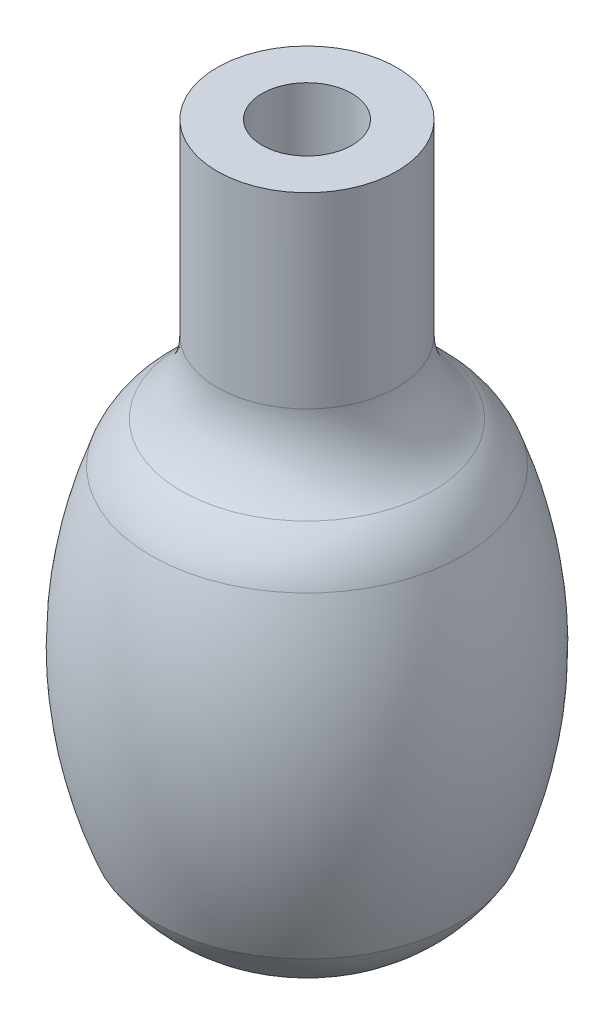
SolidWorks part; units mm, degrees
ref_plane "Front Plane" through (0, 0, 0) normal (0, 0, 1) x (1, 0, 0)
ref_plane "Top Plane" through (0, 0, 0) normal (0, 1, 0) x (1, 0, 0)
ref_plane "Right Plane" through (0, 0, 0) normal (1, 0, 0) x (0, 0, -1)
sketch "Sketch1" plane through (0, 0, 0) normal (1, 0, 0) x (0, 0, -1)
  line L0 (0, 38.8905) -> (0, -32.8262) construction
  line L1 (-5, 23.344) -> (-5, 8.344)
  line L2 (-5, 8.344) -> (-8, 8.344)
  line L3 (-5, 23.344) -> (0, 23.344)
  line L4 (0, -15.4543) -> (0, 23.344)
  spline S0 degree 2 poles (-8, 8.344) (-12.2703, -1.4236) (-8.4839, -11.108) knots 0 0 0 1 1 1
  spline S1 degree 2 poles (-8.4839, -11.108) (-5.8207, -15.4345) (0, -15.4543) knots 0 0 0 1 1 1
  dimension "D4" = 10
  dimension "D5" = 20
  dimension "D1" = 5
  dimension "D2" = 15
  dimension "D3" = 3
revolve "Revolve1" add sketch "Sketch1" angle 360 about L0
sketch "Sketch2" plane through (0, 23.344, 0) normal (0, 1, 0) x (1, 0, 0)
  circle A0 centre (0, 0) radius 2.5
  dimension "D1" = 5
extrude "Cut-Extrude1" cut sketch "Sketch2" against normal blind 15
shell "Shell4" thickness 1 removed face at (0, 8.344, 2.5)
fillet "Fillet1" radius 5 1 edges at (0, 8.344, 5)
fillet "Fillet2" radius 5 1 edges at (0, 8.344, 8)
